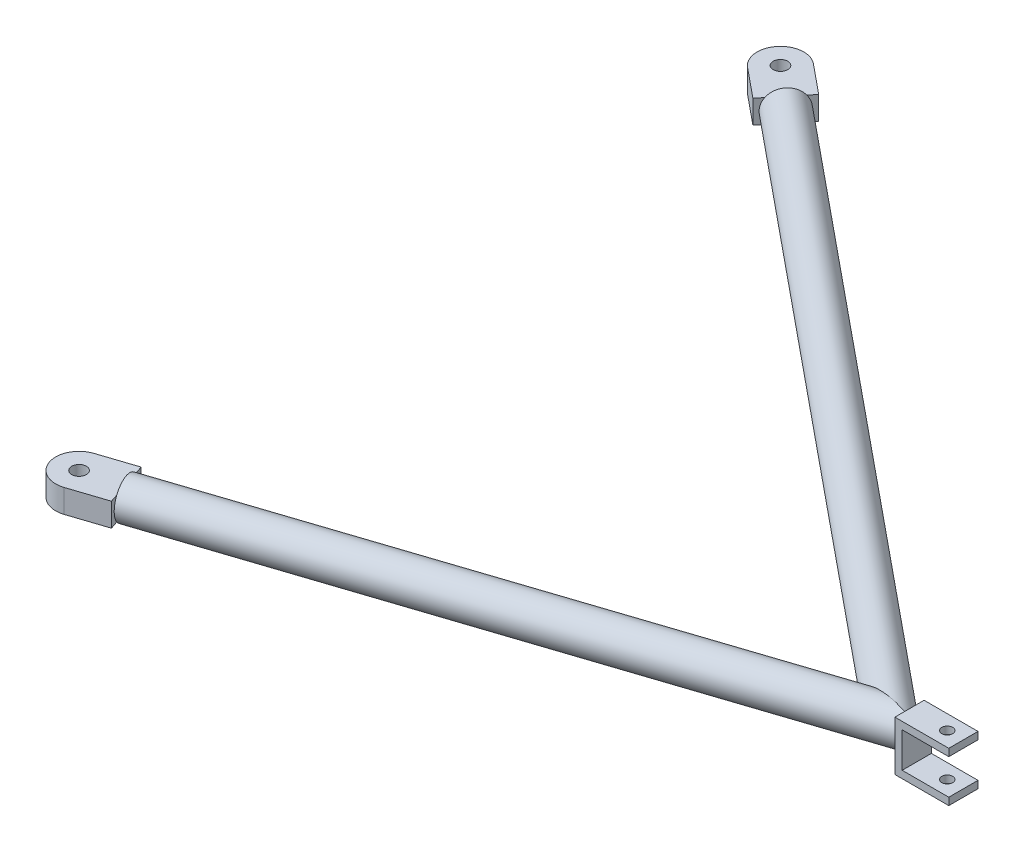
SolidWorks part; units mm, degrees
ref_plane "Front Plane" through (0, 0, 0) normal (0, 0, 1) x (1, 0, 0)
ref_plane "Top Plane" through (0, 0, 0) normal (0, 1, 0) x (1, 0, 0)
ref_plane "Right Plane" through (0, 0, 0) normal (1, 0, 0) x (0, 0, -1)
sketch "Sketch1" plane through (0, 0, 0) normal (0, 1, 0) x (1, 0, 0)
  line L0 (-265.3198, -87.5771) -> (0, 0)
  line L1 (0, 0) -> (-265.3198, 217.2229)
  line L2 (-265.3198, 217.2229) -> (-265.3198, -87.5771) construction
  dimension "D1" = 279.4
  dimension "D2" = 342.9
  dimension "D3" = 304.8
ref_plane "Plane1" through (-265.3198, 0, 87.5771) normal (0.9496, 0, -0.3134) x (-0.3134, 0, -0.9496)
sketch "Sketch2" plane through (-265.3198, 0, 87.5771) normal (0.9496, 0, -0.3134) x (-0.3134, 0, -0.9496)
  circle A0 centre (0, 0) radius 8.255
  dimension "D1" = 16.51
sweep "Sweep1" add profiles "Sketch2" path "Sketch1"
sketch "Sketch3" plane through (0, 0, 0) normal (0, 0, 1) x (1, 0, 0)
  line L0 (33.9318, 10.795) -> (10.504, 10.795)
  line L1 (10.504, 10.795) -> (10.504, -10.795)
  line L2 (10.504, -10.795) -> (33.9318, -10.795)
  line L3 (33.9318, -10.795) -> (33.9318, -7.62)
  line L4 (33.9318, -7.62) -> (13.679, -7.62)
  line L5 (13.679, -7.62) -> (13.679, 7.62)
  line L6 (13.679, 7.62) -> (33.9318, 7.62)
  line L7 (33.9318, 7.62) -> (33.9318, 10.795)
  line L8 (16.854, 0) -> (-16.854, 0) construction
  ellipse E0 centre (0, 0) end of major axis (16.854, 0) minor radius 8.255 construction
  ellipse E1 centre (0, 0) end of major axis (16.854, 0) minor radius 8.255 construction
  point P21 (10.504, 0)
  dimension "D1" = 3.175
  dimension "D2" = 15.24
  dimension "D3" = 3.175
  dimension "D4" = 6.35
extrude "Boss-Extrude1" add sketch "Sketch3" along normal blind 8.89 and the other way blind 3.81
sketch "Sketch4" plane through (-265.3198, 0, 87.5771) normal (-0.9496, 0, 0.3134) x (0.3134, 0, 0.9496)
  line L1 (-10.16, 5.08) -> (10.16, 5.08)
  line L2 (-10.16, 5.08) -> (-10.16, -5.08)
  line L3 (-10.16, -5.08) -> (10.16, -5.08)
  line L4 (10.16, 5.08) -> (10.16, -5.08)
  line L5 (-10.16, 5.08) -> (10.16, -5.08) construction
  line L6 (-10.16, -5.08) -> (10.16, 5.08) construction
  circle A1 centre (0, 0) radius 8.255
  circle A2 centre (0, 0) radius 8.255 construction
  dimension "D2" = 20.32
  dimension "D3" = 10.16
  dimension "D1" = 0
extrude "Boss-Extrude2" add sketch "Sketch4" along normal blind 10.16 and the other way blind 16.256
sketch "Sketch5" plane through (-265.3198, 0, -217.2229) normal (-0.7738, 0, -0.6335) x (-0.6335, 0, 0.7738)
  line L1 (-10.16, 5.08) -> (10.16, 5.08)
  line L2 (-10.16, 5.08) -> (-10.16, -5.08)
  line L3 (-10.16, -5.08) -> (10.16, -5.08)
  line L4 (10.16, 5.08) -> (10.16, -5.08)
  line L5 (-10.16, 5.08) -> (10.16, -5.08) construction
  line L6 (-10.16, -5.08) -> (10.16, 5.08) construction
  point P0 (0, 0)
  dimension "D1" = 20.32
  dimension "D2" = 10.16
extrude "Boss-Extrude3" add sketch "Sketch5" along normal blind 10.16 and the other way blind 16.51
sketch "Sketch6" plane through (0, 5.08, 0) normal (0, 1, 0) x (1, 0, 0)
  line L0 (-246.1089, 214.6254) -> (-266.7449, 231.5205) construction
  line L1 (-258.9814, 198.9027) -> (-279.6174, 215.7978) construction
  line L2 (-279.6174, 215.7978) -> (-266.7449, 231.5205) construction
  line L3 (-271.7561, 209.3616) -> (-279.6174, 215.7978)
  line L4 (-279.6174, 215.7978) -> (-273.1812, 223.6592)
  arc A0 (-273.1812, 223.6592) -> (-271.7561, 209.3616) centre (-265.3198, 217.2229) ccw
extrude "Cut-Extrude1" cut sketch "Sketch6" against normal through all
ref_plane "Plane2" through (0, 0, 0) normal (-0.6335, 0, 0.7738) x (0.7738, 0, 0.6335)
ref_plane "Plane3" through (0, 0, 0) normal (0.3134, 0, 0.9496) x (0.9496, 0, -0.3134)
mirror "Mirror1" about plane through (0, 0, 0) normal (-0.6335, 0, 0.7738) of "Cut-Extrude1"
sketch "Sketch7" plane through (0, 5.08, 0) normal (0, 1, 0) x (1, 0, 0)
  line L0 (-246.6984, -92.1297) -> (-271.7832, -100.4097) construction
  line L1 (-253.0677, -72.8337) -> (-278.1524, -81.1137) construction
  line L2 (-271.7832, -100.4097) -> (-278.1524, -81.1137) construction
  line L3 (-262.1352, -97.2251) -> (-271.7832, -100.4097)
  line L4 (-271.7832, -100.4097) -> (-274.9678, -90.7617)
  arc A0 (-262.1352, -97.2251) -> (-274.9678, -90.7617) centre (-265.3198, -87.5771) cw
extrude "Cut-Extrude2" cut sketch "Sketch7" against normal through all
mirror "Mirror2" about plane through (0, 0, 0) normal (0.3134, 0, 0.9496) of "Cut-Extrude2"
sketch "Sketch8" plane through (-265.3198, 0, 87.5771) normal (-0.9496, 0, 0.3134) x (0.3134, 0, 0.9496)
  line L0 (6.5068, -5.08) -> (-6.5068, -5.08) construction
  line L1 (-6.5068, 5.08) -> (6.5068, 5.08) construction
  line L2 (6.5068, -5.08) -> (-6.5068, -5.08)
  line L3 (-6.5068, 5.08) -> (6.5068, 5.08)
  arc A0 (-6.5068, -5.08) -> (6.5068, -5.08) centre (0, 0) ccw construction
  arc A1 (6.5068, 5.08) -> (-6.5068, 5.08) centre (0, 0) ccw construction
  arc A2 (-6.5068, -5.08) -> (6.5068, -5.08) centre (0, 0) ccw
  arc A3 (6.5068, 5.08) -> (-6.5068, 5.08) centre (0, 0) ccw
extrude "Cut-Extrude3" cut sketch "Sketch8" against normal up to surface (16.256 mm away) up to face at (-247.134, 0, 90.8102)
sketch "Sketch9" plane through (-265.3198, 0, -217.2229) normal (-0.7738, 0, -0.6335) x (-0.6335, 0, 0.7738)
  line L0 (6.5068, -5.08) -> (-6.5068, -5.08) construction
  line L1 (-6.5068, 5.08) -> (6.5068, 5.08) construction
  line L2 (6.5068, -5.08) -> (-6.5068, -5.08)
  line L3 (-6.5068, 5.08) -> (6.5068, 5.08)
  arc A0 (-6.5068, -5.08) -> (6.5068, -5.08) centre (0, 0) ccw construction
  arc A1 (6.5068, 5.08) -> (-6.5068, 5.08) centre (0, 0) ccw construction
  arc A2 (-6.5068, -5.08) -> (6.5068, -5.08) centre (0, 0) ccw
  arc A3 (6.5068, 5.08) -> (-6.5068, 5.08) centre (0, 0) ccw
extrude "Cut-Extrude4" cut sketch "Sketch9" against normal up to surface (16.51 mm away) up to face at (-258.1011, 0, -199.9779)
sketch "Sketch10" plane through (0, 5.08, 0) normal (0, 1, 0) x (1, 0, 0)
  point P0 (-265.3198, 217.2229)
  point P1 (-265.3198, -87.5771)
  point P3 (0, 0)
hole_wizard "E (0.25) Diameter Hole1" positions "3DSketch1" profile "Sketch11" hole size "E" standard "ANSI Inch"
sketch3d "3DSketch1"
  point P0 (-265.3198, 5.08, -217.2229)
  point P3 (-265.3198, 5.08, 87.5771)
sketch "Sketch11" plane through (-265.3198, 5.08, -217.2229) normal (1, 0, 0) x (0, 0, 1)
  line L0 (0, 0) -> (0, 20.9577)
  line L1 (0, 20.9577) -> (3.175, 19.05)
  line L2 (3.175, 19.05) -> (3.175, 0)
  line L5 (3.175, 0) -> (0, 0)
  line L10 (0, 20.9577) -> (-3.175, 19.05) construction
  line L11 (0, -6.35) -> (0, 107.95) construction
  dimension "Hole Dia." = 6.35
  dimension "Hole Depth" = 19.05
  dimension "Drill Angle" = 118
hole_wizard "3/16 (0.1875) Diameter Hole1" positions "Sketch12" profile "Sketch13" hole size "3/16" standard "ANSI Inch" end condition through all
sketch "Sketch12" plane through (0, 10.795, 0) normal (0, 1, 0) x (1, 0, 0)
  point P0 (26.9335, -2.54)
sketch "Sketch13" plane through (26.9335, 10.795, 2.54) normal (1, 0, 0) x (0, 0, 1)
  line L0 (0, 0) -> (0, 21.59)
  line L1 (0, 21.59) -> (2.3812, 21.59)
  line L2 (2.3812, 21.59) -> (2.3812, 0)
  line L5 (2.3812, 0) -> (0, 0)
  line L11 (0, -6.35) -> (0, 107.95) construction
  dimension "Thru Hole Dia." = 4.7625
  dimension "Thru Hole Depth" = 21.59
sketch "Sketch14" plane through (0, 0, 8.89) normal (0, 0, 1) x (1, 0, 0)
  line L1 (13.679, 4.8225) -> (13.679, -4.8225)
  line L2 (13.679, 4.8225) -> (13.679, -4.8225)
  ellipse E1 centre (0, 0) end of major axis (16.854, 0) minor radius 8.255 (13.679, -4.8225) -> (13.679, 4.8225) ccw
  ellipse E2 centre (0, 0) end of major axis (16.854, 0) minor radius 8.255 (13.679, -4.8225) -> (13.679, 4.8225) ccw
  dimension "D1" = 0
extrude "Cut-Extrude5" cut sketch "Sketch14" against normal through all
ref_point "Point1"
ref_point "Point2"
sketch3d "3DSketch2"
  line L0 (26.9335, 10.795, 2.54) -> (26.9335, -10.795, 2.54)
  circle A0 centre (26.9335, 10.795, 2.54) radius 2.3812 construction
  circle A1 centre (26.9335, 10.795, 2.54) radius 2.3812
  circle A2 centre (26.9335, -10.795, 2.54) radius 2.3812 construction
  circle A3 centre (26.9335, -10.795, 2.54) radius 2.3812
  point P2 (26.9335, 13.1762, 2.54)
  point P4 (26.9335, 13.1762, 2.54)
  point P7 (26.9335, -8.4138, 2.54)
  point P9 (26.9335, -8.4138, 2.54)
  point P10 (26.9335, 0, 2.54)
  point P11 (26.9335, 0, 2.54)
ref_point "Point3"
